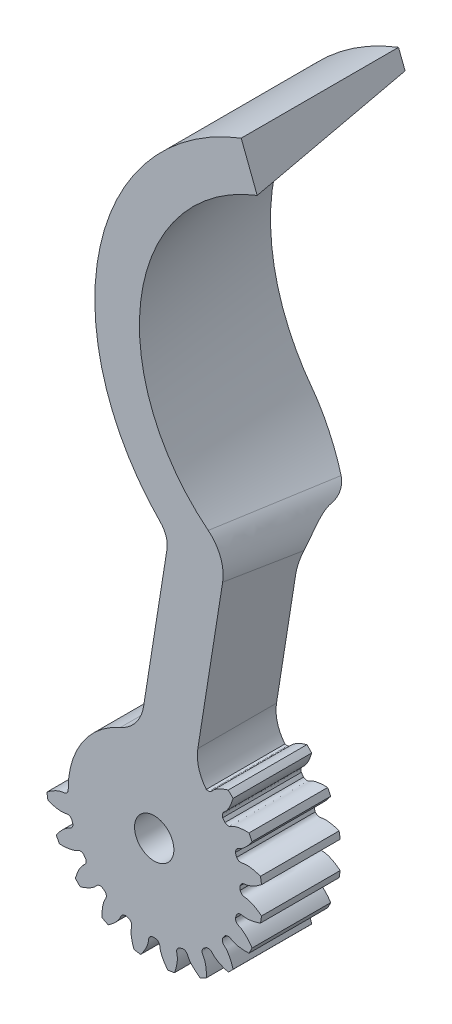
SolidWorks part; units mm, degrees
material "聚脂树脂"
ref_plane "前视基准面" through (0, 0, 0) normal (0, 0, 1) x (1, 0, 0)
ref_plane "上视基准面" through (0, 0, 0) normal (0, 1, 0) x (1, 0, 0)
ref_plane "右视基准面" through (0, 0, 0) normal (1, 0, 0) x (0, 0, -1)
other "Configuration Table"
sketch "草图1" plane through (0, 0, 0) normal (0, 0, 1) x (1, 0, 0)
  circle A0 centre (0, 0) radius 13.75
extrude "凸台-拉伸1" add sketch "草图1" along normal blind 10
ref_axis "基准轴1" through (0, 0, -1.5) along (0, 0, 1)
sketch "草图2" plane through (0, 0, 0) normal (0, 0, 1) x (1, 0, 0)
  line L0 (0, 0) -> (0, 13.75) construction
  circle A0 centre (0, 0) radius 13.75 construction
  arc A1 (0.2416, 10.9348) -> (-0.2416, 10.9348) centre (0, 0) ccw
  arc A2 (3.9764, 15.6228) -> (-3.9764, 15.6228) centre (0, 0) ccw
  spline S0 degree 3 poles (0.2416, 10.9348) (0.764, 11.1168) (0.6964, 11.4839) (0.7661, 11.8375) (0.7736, 11.8719) (0.7829, 11.9108) (0.7941, 11.954) (0.8075, 12.0015) (0.8231, 12.0532) (0.8413, 12.1091) (0.8621, 12.169) (0.8857, 12.2329) (0.9123, 12.3007) (0.9421, 12.3723) (0.9752, 12.4476) (1.0117, 12.5264) (1.0519, 12.6088) (1.0959, 12.6945) (1.1438, 12.7834) (1.1957, 12.8755) (1.2519, 12.9705) (1.3125, 13.0684) (1.3775, 13.1691) (1.4472, 13.2723) (1.5216, 13.3779) (1.601, 13.4858) (1.6853, 13.5958) (1.7747, 13.7078) (1.8694, 13.8216) (1.9693, 13.937) (2.0748, 14.0539) (2.1857, 14.1721) (2.3023, 14.2914) (2.4246, 14.4116) (2.5527, 14.5326) (2.6866, 14.6542) (2.8265, 14.7761) (2.9725, 14.8983) (3.1245, 15.0204) (3.2826, 15.1424) (3.4469, 15.2639) (3.6768, 15.427) (3.8549, 15.5454) (3.9764, 15.6228) knots 0 0 0 0 0.165916 0.170906 0.176664 0.183189 0.190482 0.198542 0.207371 0.216967 0.22733 0.238462 0.250361 0.263027 0.276462 0.290664 0.305634 0.321371 0.337876 0.355149 0.37319 0.391998 0.411574 0.431917 0.453028 0.474907 0.497554 0.520968 0.54515 0.570099 0.595817 0.622302 0.649554 0.677575 0.706363 0.735918 0.766242 0.797333 0.829191 0.861818 0.895212 0.929373 1 1 1 1
  spline S1 degree 3 poles (-0.2416, 10.9348) (-0.764, 11.1168) (-0.6964, 11.4839) (-0.7661, 11.8375) (-0.7736, 11.8719) (-0.7829, 11.9108) (-0.7941, 11.954) (-0.8075, 12.0015) (-0.8231, 12.0532) (-0.8413, 12.1091) (-0.8621, 12.169) (-0.8857, 12.2329) (-0.9123, 12.3007) (-0.9421, 12.3723) (-0.9752, 12.4476) (-1.0117, 12.5264) (-1.0519, 12.6088) (-1.0959, 12.6945) (-1.1438, 12.7834) (-1.1957, 12.8755) (-1.2519, 12.9705) (-1.3125, 13.0684) (-1.3775, 13.1691) (-1.4472, 13.2723) (-1.5216, 13.3779) (-1.601, 13.4858) (-1.6853, 13.5958) (-1.7747, 13.7078) (-1.8694, 13.8216) (-1.9693, 13.937) (-2.0748, 14.0539) (-2.1857, 14.1721) (-2.3023, 14.2914) (-2.4246, 14.4116) (-2.5527, 14.5326) (-2.6866, 14.6542) (-2.8265, 14.7761) (-2.9725, 14.8983) (-3.1245, 15.0204) (-3.2826, 15.1424) (-3.4469, 15.2639) (-3.6768, 15.427) (-3.8549, 15.5454) (-3.9764, 15.6228) knots 0 0 0 0 0.165916 0.170906 0.176664 0.183189 0.190482 0.198542 0.207371 0.216967 0.22733 0.238462 0.250361 0.263027 0.276462 0.290664 0.305634 0.321371 0.337876 0.355149 0.37319 0.391998 0.411574 0.431917 0.453028 0.474907 0.497554 0.520968 0.54515 0.570099 0.595817 0.622302 0.649554 0.677575 0.706363 0.735918 0.766242 0.797333 0.829191 0.861818 0.895212 0.929373 1 1 1 1
extrude "切除-拉伸1" cut sketch "草图2" along normal through all
pattern_circular "阵列(圆周)1" count 20 every 18 about axis through (0, 0, -1.5) along (0, 0, 1) of "切除-拉伸1"
sketch "草图6" plane through (0, 0, 0) normal (0, 0, -1) x (-1, 0, 0)
  line L0 (0, 0) -> (-10.311, 65.1009) construction
  line L1 (0, 0) -> (38.9643, 6.1713) construction
  line L2 (0, 0) -> (-30.4582, -4.8241) construction
  line L3 (-12.3461, -1.9554) -> (-21.1812, 53.827) construction
  line L4 (3.4569, 0.5475) -> (-2.1703, 36.0761)
  line L5 (-3.4569, -0.5475) -> (-9.0841, 34.981)
  line L6 (-9.0841, 34.981) -> (-15.0031, 72.3522)
  line L7 (-15.0031, 72.3522) -> (-21.4537, 55.5478) construction
  line L8 (-15.0031, 72.3522) -> (-7.9754, 90.6601) construction
  line L9 (-15.0031, 72.3522) -> (-11.6329, 81.132)
  line L10 (-3.4569, -0.5475) -> (3.4569, 0.5475)
  line L11 (-11.061, 82.6216) -> (-11.6329, 81.132)
  circle A0 centre (0, 0) radius 12.5 construction
  circle A1 centre (-21.4537, 55.5478) radius 24 construction
  circle A2 centre (-21.4537, 55.5478) radius 27.4044 construction
  arc A3 (-11.6329, 81.132) -> (-2.1703, 36.0761) centre (-21.4537, 55.5478) cw
  arc A4 (-12.8529, 77.9537) -> (-9.0841, 34.981) centre (-21.4537, 55.5478) cw
  circle A5 centre (-21.4537, 55.5478) radius 29 construction
  arc A6 (-11.061, 82.6216) -> (-1.8671, 34.1617) centre (-21.4537, 55.5478) cw
  dimension "D1" = 25
  dimension "D4" = 48
  dimension "D5" = 30
  dimension "D6" = 58
  dimension "D2" = 7
  dimension "D3" = 58.22
extrude "凸台-拉伸2" add sketch "草图6" against normal blind 10 and the other way blind 10 contours A3 L9 L6 L5 L10 L4 | L5 | L4 | A4 L9 L6 region at (0.1311, 0.8278, 0) region at (1.5039, 35.2004, 0) region at (6.2688, 57.529, 0)
sketch "草图7" plane through (-3.4569, 0.5475, 0) normal (0.9877, -0.1564, 0) x (0, 0, -1)
  line L0 (0, 0) -> (0, 34)
  line L1 (0, 34) -> (10, 34)
  line L3 (10, 34) -> (10, 0)
  line L4 (10, 0) -> (0, 0) construction
  line L5 (10, 0) -> (10, 73.8085) construction
  line L6 (10, 0) -> (0, 0)
  line L7 (-5, 4.6588) -> (-5, 27.3083) construction
  line L8 (-10, 4.6588) -> (0, 4.6588) construction
  line L9 (-20, 34) -> (-20, 0)
  line L10 (-10, 34) -> (-20, 34)
  line L11 (-10, 0) -> (-10, 34)
  line L12 (-20, 0) -> (-10, 0)
  dimension "D1" = 34
extrude "切除-拉伸3" cut sketch "草图7" against normal blind 32 and the other way blind 10
ref_plane "基准面1" through (12.5, 0, 0) normal (1, 0, 0) x (0, 0, -1)
ref_axis "基准轴2" through (0, 0, -6) along (0, 0, 1)
ref_plane "基准面2" through (0, 0, 0) normal (-0.9877, 0.1564, 0) x (0, 0, 1)
ref_plane "基准面3" through (12.3461, -1.9554, 0) normal (-0.9877, 0.1564, 0) x (0, 0, 1)
sketch "草图16" plane through (0, 0, 10) normal (0, 0, 1) x (1, 0, 0)
  circle A0 centre (0, 0) radius 2.5
  dimension "D1" = 5
extrude "切除-拉伸5" cut sketch "草图16" against normal blind 16.5
sketch "草图19" plane through (0, 0, 0) normal (0, 0, -1) x (-1, 0, 0)
  circle A0 centre (0, 0) radius 8
  dimension "D1" = 16
extrude "切除-拉伸7" cut sketch "草图19" against normal blind 3.4
sketch "草图20" plane through (0, 0, 0) normal (0, 0, -1) x (-1, 0, 0)
  line L0 (0, 0) -> (3.6089, 10.325)
  line L1 (3.6089, 10.325) -> (7.1451, 20.4421)
  line L2 (0, 0) -> (10.9348, -0.2416)
  line L3 (10.9348, -0.2416) -> (20.7519, -0.2416)
  circle A0 centre (0, 0) radius 17.5
  circle A1 centre (0, 0) radius 10.9375
  arc A2 (-8.7044, 6.6228) -> (-8.9885, 6.2318) centre (0, 0) ccw construction
  dimension "D1" = 35
extrude "切除-拉伸8" cut sketch "草图20" against normal blind 10 contours A1 L3 A0 L1 region at (-11.1082, 7.7459, 0)
sketch "草图23" plane through (0, 0, 10) normal (0, 0, 1) x (1, 0, 0)
  line L0 (-1.4427, 13.2649) -> (-1.8359, 10.7823)
  line L1 (1.8671, 34.1617) -> (-1.4427, 13.2649) construction
  line L2 (5.4711, 12.1699) -> (5.0779, 9.6873)
  line L3 (15.0031, 72.3522) -> (5.4711, 12.1699) construction
  circle A0 centre (0, 0) radius 10.9375
  arc A1 (-1.7221, 13.6417) -> (-2.5777, 13.5062) centre (0, 0) ccw construction
  arc A2 (-1.7221, 13.6417) -> (-2.5777, 13.5062) centre (0, 0) ccw
  arc A3 (6.6252, 12.0486) -> (5.8534, 12.4419) centre (0, 0) ccw construction
  arc A4 (6.6252, 12.0486) -> (5.8534, 12.4419) centre (0, 0) ccw
  spline S0 degree 3 poles (996.9007, 66.1041) (-88.8946, -5.2942) (-13.4757, 28.9809) (-1.601, 13.4858) (-1.5216, 13.3779) (7.2871, 0.8786) (-29.1617, -42.7887) (-976.2266, -209.8124) knots -9.021595 -9.021595 -9.021595 -9.021595 0.502446 0.525093 0.546972 0.568083 8.020067 8.020067 8.020067 8.020067 only from (-1.7221, 13.6417) to (-1.4427, 13.2649) construction
  spline S1 degree 3 poles (-1001.8702, -39.9652) (14.2454, 6.0691) (-2.4742, 7.7001) (-2.931, 11.5081) (-2.9354, 11.558) (-2.9398, 11.6323) (-2.9424, 11.7223) (-2.941, 11.8445) (-2.9339, 11.9853) (-2.9194, 12.1444) (-2.8961, 12.3215) (-2.8626, 12.516) (-2.8175, 12.7274) (-2.7593, 12.9551) (-2.6999, 13.1539) (-2.6447, 13.3205) (3.8605, 31.7266) (86.1798, 22.4348) (-968.5361, -245.1905) knots -1.696649 -1.696649 -1.696649 -1.696649 0.165916 0.170906 0.183189 0.190482 0.207371 0.22733 0.250361 0.276462 0.305634 0.337876 0.37319 0.411574 0.453028 0.474907 0.497554 10.021595 10.021595 10.021595 10.021595 only from (-3.1492, 10.4743) to (-2.5777, 13.5062) construction
  spline S2 degree 3 poles (-1.7221, 13.6417) (-1.653, 13.5549) (-1.5584, 13.4302) (-1.4684, 13.3023) (-1.4427, 13.2649) knots 0.492568 0.492568 0.492568 0.492568 0.546972 0.569233 0.569233 0.569233 0.569233
  spline S3 degree 3 poles (-3.1492, 10.4743) (-2.7087, 10.8088) (-2.8864, 11.137) (-2.931, 11.5081) (-2.9354, 11.558) (-2.9398, 11.6323) (-2.9424, 11.7223) (-2.941, 11.8445) (-2.9339, 11.9853) (-2.9194, 12.1444) (-2.8961, 12.3215) (-2.8626, 12.516) (-2.8175, 12.7274) (-2.7593, 12.9551) (-2.6866, 13.1982) (-2.6232, 13.3832) (-2.5848, 13.4873) (-2.5777, 13.5062) knots 0 0 0 0 0.165916 0.170906 0.183189 0.190482 0.207371 0.22733 0.250361 0.276462 0.305634 0.337876 0.37319 0.411574 0.453028 0.497554 0.507432 0.507432 0.507432 0.507432
  spline S4 degree 3 poles (845.3644, -532.484) (-75.0291, 47.9678) (6.1325, 31.3668) (6.6326, 11.8082) (6.6318, 11.5928) (6.6211, 11.3487) (6.6022, 11.1239) (6.5767, 10.9187) (6.5461, 10.7332) (6.5119, 10.5675) (6.4757, 10.4216) (6.4439, 10.3125) (6.4137, 10.2194) (6.3905, 10.1545) (6.3633, 10.0853) (6.3437, 10.0391) (4.7326, 6.5586) (-11.6727, 10.1742) (940.4849, -347.6039) knots -9.021595 -9.021595 -9.021595 -9.021595 0.502446 0.525093 0.568083 0.608002 0.644851 0.678629 0.709336 0.736973 0.761538 0.783033 0.792629 0.809518 0.816811 0.829094 0.834084 2.696649 2.696649 2.696649 2.696649 only from (6.6252, 12.0486) to (6.2318, 8.9885) construction
  spline S5 degree 3 poles (863.6255, -501.2219) (14.5123, -49.7066) (-6.659, 3.0874) (5.5812, 12.2529) (5.6899, 12.331) (21.7716, 23.3982) (82.9074, -32.5047) (-927.6723, 370.9243) knots -7.020109 -7.020109 -7.020109 -7.020109 0.431917 0.453028 0.474907 0.497554 10.021566 10.021566 10.021566 10.021566 only from (5.4711, 12.1699) to (5.8534, 12.4419) construction
  spline S6 degree 3 poles (6.6252, 12.0486) (6.6301, 11.9377) (6.6341, 11.7422) (6.6276, 11.4683) (6.6126, 11.2338) (6.5902, 11.0188) (6.5619, 10.8235) (6.5293, 10.6479) (6.4939, 10.4921) (6.4623, 10.3749) (6.4317, 10.2737) (6.4078, 10.2024) (6.3839, 10.1378) (6.3633, 10.0853) (6.3437, 10.0391) (6.1867, 9.7) (5.9162, 9.4428) (6.2318, 8.9885) knots 0.492568 0.492568 0.492568 0.492568 0.546972 0.588426 0.62681 0.662124 0.694366 0.723538 0.749639 0.77267 0.783033 0.801458 0.809518 0.816811 0.829094 0.834084 1 1 1 1
  spline S7 degree 3 poles (5.4711, 12.1699) (5.5426, 12.2247) (5.6688, 12.3172) (5.798, 12.4053) (5.8534, 12.4419) knots 0.430767 0.430767 0.430767 0.430767 0.474907 0.507432 0.507432 0.507432 0.507432
extrude "切除-拉伸10" cut sketch "草图23" against normal blind 10 contours S3 A0 L0 S2 A2 | S7 L2 A0 S6 A4 region at (-2.2448, 12.1367, 10) region at (5.8854, 10.849, 10)
fillet "圆角7" radius 5 2 edges at (5.0779, 9.6873, 5) (-1.8359, 10.7823, 5)
ref_axis "基准轴4" through (0, 0, -6.3479) along (0, 0, 1)
ref_plane "基准面5" through (0, 0, 0) normal (-0.1564, -0.9877, 0) x (0, 0, 1)
ref_plane "基准面6" through (9.1076, 57.5032, 0) normal (-0.1564, -0.9877, 0) x (0, 0, 1)
ref_axis "基准轴5" through (21.4537, 55.5478, -7.1) along (0, 0, 1)
sketch "草图25" plane through (12.3461, -1.9554, 0) normal (0.9877, -0.1564, 0) x (0, 0, -1)
  line L0 (0, 0) -> (30.8675, 0) construction
  line L1 (-45.5232, 58.22) -> (43.0434, 58.22) construction
  line L6 (0, 13.3716) -> (0, 103.0684) construction
  line L8 (-10, 73.8739) -> (-10, 97.9715) construction
  line L9 (-10, 13.3716) -> (-10, 73.8085) construction
  line L10 (10, 74.5354) -> (10, 100.334) construction
  line L11 (10, 34) -> (10, 73.8085) construction
  line L12 (0, 13.3716) -> (0, 34) construction
  line L72 (-30, 58.22) -> (30, 58.22)
  line L73 (-30, 78.22) -> (-30, 58.22)
  line L74 (30, 88.22) -> (-30, 78.22)
  line L75 (30, 58.22) -> (30, 88.22)
  point P7 (0, 58.22)
  point P8 (30.4083, 88.22)
  dimension "D1" = 58.22
  dimension "D2" = 20
  dimension "D3" = 30
  dimension "D4" = 60
revolve "切除-旋转1" cut sketch "草图25" angle 360 about axis through (21.4537, 55.5478, -7.1) along (0, 0, 1) region at (23.4352, 68.0585, -2)
fillet "圆角9" radius 3 1 edges at (1.8671, 34.1617, 0)
fillet "圆角10" radius 5 2 edges at (5.112, 33.6142, 0) (4.0462, 33.783, -10)
fillet "圆角11" radius 5 1 edges
